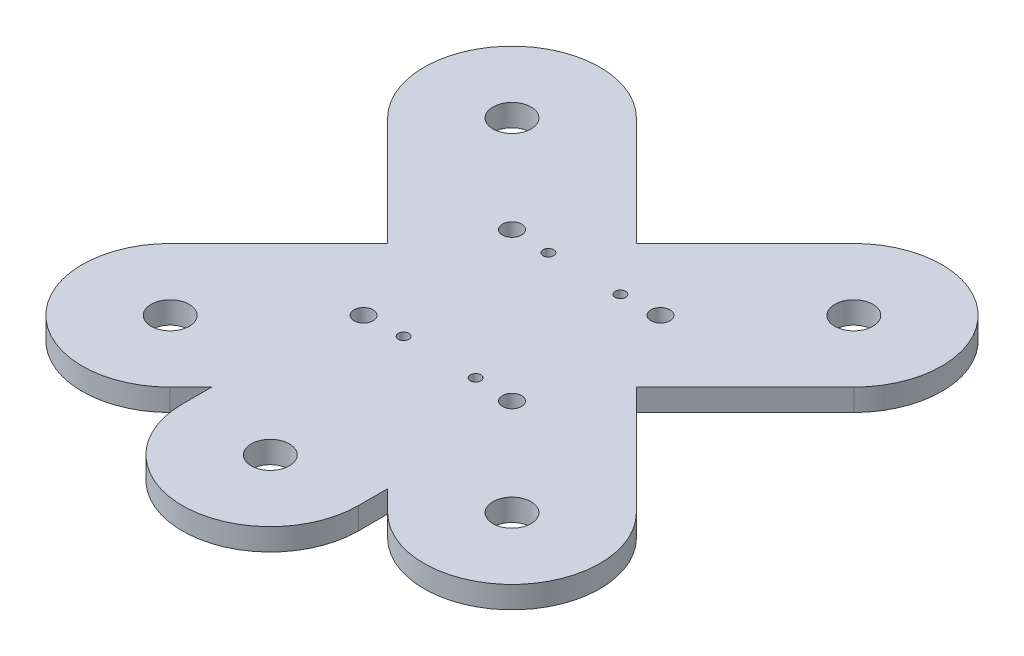
SolidWorks part; units mm, degrees
ref_plane "Front" through (0, 0, 0) normal (0, 0, 1) x (1, 0, 0)
ref_plane "Top" through (0, 0, 0) normal (0, 1, 0) x (1, 0, 0)
ref_plane "Right" through (0, 0, 0) normal (1, 0, 0) x (0, 0, -1)
sketch "Esquisse2" plane through (0, 0, 0) normal (0, 1, 0) x (1, 0, 0)
  line L0 (-30, 30) -> (30, -30) construction
  line L1 (30, 30) -> (30, -30) construction
  line L2 (30, -30) -> (-30, -30) construction
  line L3 (-30, -30) -> (-30, 30) construction
  line L4 (-30, 30) -> (30, 30) construction
  line L5 (30, 30) -> (-30, -30) construction
  line L6 (-1.7157, 1.7157) -> (-58.2843, 58.2843) construction
  line L7 (-22.9289, -19.4975) -> (-79.4975, 37.0711)
  line L8 (19.4975, 22.9289) -> (-37.0711, 79.4975)
  line L11 (5, 11.5685) -> (5, 91.5685) construction
  line L15 (1.7157, 1.7157) -> (58.2843, 58.2843) construction
  line L16 (-19.4975, 22.9289) -> (37.0711, 79.4975)
  line L17 (21.5685, -5) -> (101.5685, -5) construction
  line L20 (22.9289, -19.4975) -> (79.4975, 37.0711)
  line L28 (1.7157, -1.7157) -> (58.2843, -58.2843) construction
  line L29 (-11.5685, -5) -> (-91.5685, -5) construction
  line L30 (22.9289, 19.4975) -> (79.4975, -37.0711)
  line L31 (-19.4975, -22.9289) -> (37.0711, -79.4975)
  line L32 (0, -2.4264) -> (0, -82.4264) construction
  line L33 (30, -2.4264) -> (30, -82.4264)
  line L34 (-30, -2.4264) -> (-30, -82.4264)
  line L35 (-1.7157, -1.7157) -> (-58.2843, -58.2843) construction
  line L36 (19.4975, -22.9289) -> (-37.0711, -79.4975)
  line L37 (-22.9289, 19.4975) -> (-79.4975, -37.0711)
  line L59 (0, 2.4264) -> (0, 82.4264) construction
  line L60 (-30, 2.4264) -> (-30, 82.4264)
  line L61 (30, 2.4264) -> (30, 82.4264)
  line L62 (2.4264, 0) -> (82.4264, 0) construction
  line L63 (2.4264, 30) -> (82.4264, 30)
  line L64 (2.4264, -30) -> (82.4264, -30)
  line L65 (-2.4264, 0) -> (-82.4264, 0) construction
  line L66 (-2.4264, -30) -> (-82.4264, -30)
  line L67 (-2.4264, 30) -> (-82.4264, 30)
  line L68 (0, 2.4264) -> (0, 82.4264) construction
  line L69 (-30, 2.4264) -> (-30, 82.4264)
  line L70 (30, 2.4264) -> (30, 82.4264)
  line L71 (2.4264, 0) -> (82.4264, 0) construction
  line L72 (2.4264, 30) -> (82.4264, 30)
  line L73 (2.4264, -30) -> (82.4264, -30)
  line L74 (-2.4264, 0) -> (-82.4264, 0) construction
  line L75 (-2.4264, -30) -> (-82.4264, -30)
  line L76 (-2.4264, 30) -> (-82.4264, 30)
  arc A0 (-22.9289, -19.4975) -> (19.4975, 22.9289) centre (-1.7157, 1.7157) ccw
  arc A1 (-37.0711, 79.4975) -> (-79.4975, 37.0711) centre (-58.2843, 58.2843) ccw
  arc A6 (-19.4975, 22.9289) -> (22.9289, -19.4975) centre (1.7157, 1.7157) ccw
  arc A7 (79.4975, 37.0711) -> (37.0711, 79.4975) centre (58.2843, 58.2843) ccw
  arc A16 (22.9289, 19.4975) -> (-19.4975, -22.9289) centre (1.7157, -1.7157) ccw
  arc A17 (37.0711, -79.4975) -> (79.4975, -37.0711) centre (58.2843, -58.2843) ccw
  arc A18 (30, -2.4264) -> (-30, -2.4264) centre (0, -2.4264) ccw
  arc A19 (-30, -82.4264) -> (30, -82.4264) centre (0, -82.4264) ccw
  arc A20 (19.4975, -22.9289) -> (-22.9289, 19.4975) centre (-1.7157, -1.7157) ccw
  arc A21 (-79.4975, -37.0711) -> (-37.0711, -79.4975) centre (-58.2843, -58.2843) ccw
  arc A42 (-30, 2.4264) -> (30, 2.4264) centre (0, 2.4264) ccw
  arc A43 (30, 82.4264) -> (-30, 82.4264) centre (0, 82.4264) ccw
  arc A44 (2.4264, 30) -> (2.4264, -30) centre (2.4264, 0) ccw
  arc A45 (82.4264, -30) -> (82.4264, 30) centre (82.4264, 0) ccw
  arc A46 (-2.4264, -30) -> (-2.4264, 30) centre (-2.4264, 0) ccw
  arc A47 (-82.4264, 30) -> (-82.4264, -30) centre (-82.4264, 0) ccw
  point P0 (0, 0)
  point P9 (-30, 30)
  point P19 (5, 51.5685)
  point P22 (0, 49.4975)
  point P29 (30, 30)
  point P33 (61.5685, -5)
  point P39 (49.4975, 0)
  point P46 (30, -30)
  point P53 (0, -42.4264)
  point P61 (-51.5685, -5)
  point P63 (-30, -30)
  point P66 (5, -5)
  point P71 (-49.4975, 0)
  point P76 (0, 0)
  point P109 (0, 49.4975)
  point P116 (49.4975, 0)
  point P123 (-49.4975, 0)
  point P130 (0, 42.4264)
  point P137 (42.4264, 0)
  point P144 (-42.4264, 0)
  point P151 (0, 42.4264)
  point P158 (42.4264, 0)
  point P165 (-42.4264, 0)
  point P172 (0, 42.4264)
  point P179 (42.4264, 0)
  point P186 (-42.4264, 0)
  dimension "D4" = 30
  dimension "D1" = 60
  dimension "D2" = 60
  dimension "D3" = 80
  dimension "D5" = 8
extrude "Boss.-Extru.1" add sketch "Esquisse2" along normal blind 7.5 contours A17 | L36 A21 L37 A20 | L33 A19 L34 A18 | L30 A17 L31 A16 | L8 A1 L7 A0 | L16 A7 L20 A6
sketch "Esquisse4" plane through (0, 0, 0) normal (0, -1, 0) x (-1, 0, 0)
  line L0 (0, 0) -> (-79.4975, -79.4975) construction
  line L1 (-25.317, -46.5302) -> (-7.6393, -28.8525)
  line L2 (-7.6393, -28.8525) -> (-28.8525, -7.6393)
  line L3 (-28.8525, -7.6393) -> (-46.5302, -25.317)
  line L4 (-42.4264, 0) -> (-79.4975, -37.0711) construction
  line L5 (-46.5302, 25.317) -> (-28.8525, 7.6393)
  line L6 (-7.6393, 28.8525) -> (-25.317, 46.5302)
  line L7 (-28.8525, 7.6393) -> (-7.6393, 28.8525)
  line L8 (25.317, 46.5302) -> (7.6393, 28.8525)
  line L9 (28.8525, 7.6393) -> (46.5302, 25.317)
  line L10 (7.6393, 28.8525) -> (28.8525, 7.6393)
  line L11 (46.5302, -25.317) -> (28.8525, -7.6393)
  line L12 (7.6393, -28.8525) -> (25.317, -46.5302)
  line L13 (28.8525, -7.6393) -> (7.6393, -28.8525)
  arc A0 (-79.4975, -37.0711) -> (-37.0711, -79.4975) centre (-58.2843, -58.2843) ccw construction
  arc A1 (-25.317, -46.5302) -> (-46.5302, -25.317) centre (-58.2843, -58.2843) ccw
  arc A2 (-46.5302, 25.317) -> (-25.317, 46.5302) centre (-58.2843, 58.2843) ccw
  arc A3 (25.317, 46.5302) -> (46.5302, 25.317) centre (58.2843, 58.2843) ccw
  arc A4 (46.5302, -25.317) -> (25.317, -46.5302) centre (58.2843, -58.2843) ccw
  point P36 (0, 0)
  dimension "D5" = 35
  dimension "D1" = 25
  dimension "D2" = 25
  dimension "D3" = 15
  dimension "D4" = 30
extrude "Enlèv. mat.-Extru.1" cut sketch "Esquisse4" against normal blind 2 contours L0 L2 L3 A1 | L2 L0 A1 L1 | A2 L5 L7 L6 | A3 L8 L10 L9 | A4 L11 L13 L12 region at (20.863, 0, 31.7295) region at (31.7295, 0, 20.863) region at (26.2963, 0, -26.2963) region at (-26.2963, 0, -26.2963) region at (-26.2963, 0, 26.2963)
sketch "Esquisse5" plane through (0, 2, 0) normal (0, -1, 0) x (-1, 0, 0)
  line L0 (0, 0) -> (-58.2843, -58.2843) construction
  line L1 (-58.2843, -58.2843) -> (0, 0) construction
  line L2 (-7.6393, -28.8525) -> (-28.8525, -7.6393) construction
  circle A0 centre (-25.317, -25.317) radius 3.25
  circle A1 centre (-25.317, 25.317) radius 3.25
  circle A2 centre (25.317, 25.317) radius 3.25
  circle A3 centre (25.317, -25.317) radius 3.25
  point P17 (0, 0)
  dimension "D1" = 6.5
  dimension "D2" = 10
extrude "Enlèv. mat.-Extru.2" cut sketch "Esquisse5" against normal through all
sketch "Esquisse7" plane through (0, 0, 0) normal (0, -1, 0) x (-1, 0, 0)
  circle A0 centre (0, -82.4264) radius 6.5
  circle A1 centre (-58.2843, -58.2843) radius 6.5
  circle A2 centre (-82.4264, 0) radius 6.5 [skipped]
  circle A3 centre (-58.2843, 58.2843) radius 6.5
  circle A4 centre (0, 82.4264) radius 6.5 [skipped]
  circle A5 centre (58.2843, 58.2843) radius 6.5
  circle A6 centre (82.4264, 0) radius 6.5 [skipped]
  circle A7 centre (58.2843, -58.2843) radius 6.5
  point P20 (0, 0)
  dimension "D1" = 13
extrude "Enlèv. mat.-Extru.3" cut sketch "Esquisse7" against normal through all
sketch "Sketch2" plane through (0, 7.5, 0) normal (0, 1, 0) x (1, 0, 0)
  line L0 (-12.275, 24.675) -> (12.275, 24.675) construction
  line L1 (12.275, 24.675) -> (12.275, -24.675) construction
  line L2 (12.275, -24.675) -> (-12.275, -24.675) construction
  line L3 (-12.275, -24.675) -> (-12.275, 24.675) construction
  circle A0 centre (-12.275, 24.675) radius 1.8
  circle A1 centre (12.275, 24.675) radius 1.8
  circle A2 centre (-12.275, -24.675) radius 1.8
  circle A3 centre (12.275, -24.675) radius 1.8
  dimension "D5" = 3.6
  dimension "D6" = 3.6
  dimension "D7" = 3.6
  dimension "D8" = 3.6
  dimension "D1" = 49.35
  dimension "D2" = 24.55
  dimension "D3" = 12.275
  dimension "D4" = 24.675
extrude "Cut-Extrude1" cut sketch "Sketch2" against normal up to surface (7.5 mm away) up to face at (0, 0, 75.9264)
